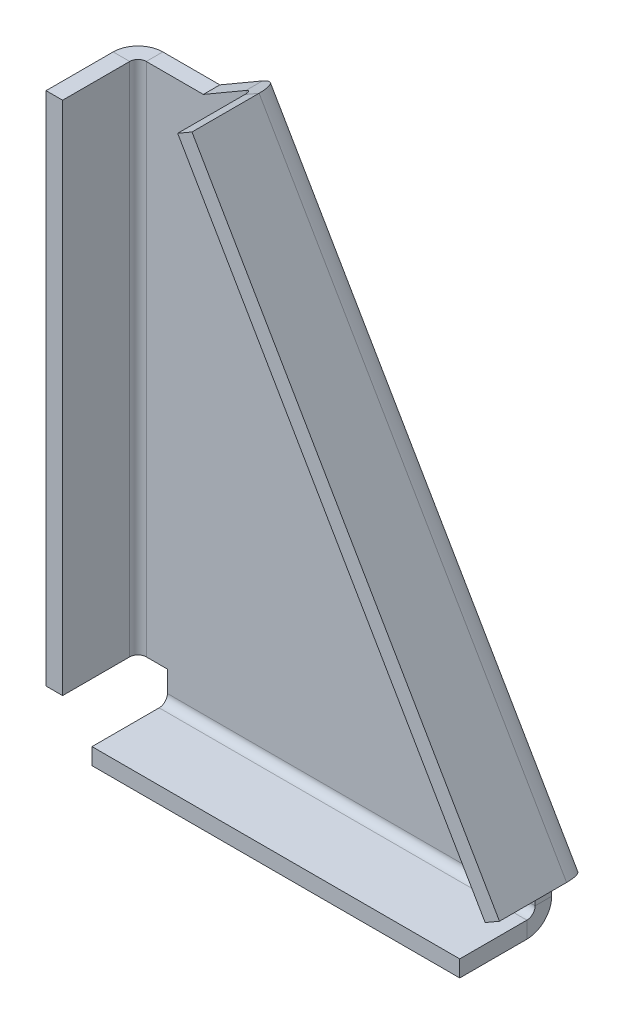
SolidWorks part; units mm, degrees
note: The reader was unsure of these and kept them because the rebuilt part matched: flange length of "Edge-Flange1".
material "6061 Alloy"
ref_plane "Front Plane" through (0, 0, 0) normal (0, 0, 1) x (1, 0, 0)
ref_plane "Top Plane" through (0, 0, 0) normal (0, 1, 0) x (1, 0, 0)
ref_plane "Right Plane" through (0, 0, 0) normal (1, 0, 0) x (0, 0, -1)
sketch "Sketch1" plane through (0, 0, 0) normal (0, 0, 1) x (1, 0, 0)
  line L0 (0, 0) -> (0, -6.35)
  line L1 (0, -6.35) -> (50.8, -6.35)
  line L2 (50.8, -6.35) -> (50.8, 0)
  line L3 (50.8, 0) -> (56.2919, 3.1877)
  line L4 (56.2919, 3.1877) -> (13.8112, 76.3748)
  line L5 (13.8112, 76.3748) -> (4.9644, 71.2397)
  line L6 (4.9644, 71.2397) -> (-6.35, 71.2397)
  line L7 (-6.35, 71.2397) -> (-6.35, 0)
  line L8 (-6.35, 0) -> (0, 0)
  point P10 (9.4496, 71.2397)
  point P11 (4.9644, 71.2397)
  dimension "D1" = 50.8
  dimension "D3" = 6.35
base flange "Base-Flange1" sketch "Sketch1" thickness 2.286 reverse thickness direction no parameters "D1"=1.143
edge flange "Edge-Flange1" sketch "Sketch12" flange profiles "Sketch12", "Sketch13", "Sketch14" flange angle 90 flange length 12.7 flange position material inside bend radius 1.143 thickness 2.286 relief rectangular gap distance 1 parameters "D6"=10, "D8"=1
sketch "Sketch12" plane through (-6.35, 0, 0) normal (-1, 0, 0) x (0, -1, 0)
  line L0 (-71.2397, 0) -> (0, 0) construction
  line L1 (-71.2397, 0) -> (0, 0)
  line L2 (-71.2397, 0) -> (-71.2397, 10.414)
  line L3 (-71.2397, 10.414) -> (0, 10.414)
  line L4 (0, 10.414) -> (0, 0)
sketch "Sketch13" plane through (0, -6.35, 0) normal (0, -1, 0) x (1, 0, 0)
  line L0 (0, 0) -> (50.8, 0) construction
  line L1 (0, 0) -> (50.8, 0)
  line L2 (0, 0) -> (0, 10.414)
  line L3 (0, 10.414) -> (50.8, 10.414)
  line L4 (50.8, 10.414) -> (50.8, 0)
sketch "Sketch14" plane through (43.4899, 25.2433, 0) normal (0.8649, 0.502, 0) x (-0.502, 0.8649, 0)
  line L0 (-25.5018, 0) -> (59.1207, 0) construction
  line L1 (-25.5018, 0) -> (59.1207, 0)
  line L2 (-25.5018, 0) -> (-25.5018, 10.414)
  line L3 (-25.5018, 10.414) -> (59.1207, 10.414)
  line L4 (59.1207, 10.414) -> (59.1207, 0)
bend "EdgeBend1" bend radius 1.143 bend angle 90 parameters "D5"=1
bend "EdgeBend2" bend radius 1.143 bend angle 90 parameters "D5"=2
bend "EdgeBend3" bend radius 1.143 bend angle 90 parameters "D5"=3
sketch "Bend-Lines1" [suppressed] plane through (0, 0, 0) normal (0, 1, 0) x (1, 0, 0)
sketch "Bounding-Box1" [suppressed] plane through (0, 0, 0) normal (0, 1, 0) x (1, 0, 0)
sheet metal parameters "Sheet-Metal1" thickness 2.286 parameters "D1"=1.143
flat pattern "Flat-Pattern1" [suppressed]
sketch "Bend-Lines2" plane through (0, 0, 0) normal (0, 1, 0) x (1, 0, 0)
sketch3d "Bounding-Box2" [suppressed]
  line L0 (-68.6901, 88.5048, 0) -> (-68.6901, -6.35, 0) construction
  line L1 (6.35, 88.5048, 0) -> (6.35, -6.35, 0) construction
  line L2 (-68.6901, 88.5048, 0) -> (6.35, 88.5048, 0) construction
  line L3 (-68.6901, -6.35, 0) -> (6.35, -6.35, 0) construction
sheet metal parameters "Sheet-Metal2" thickness 2.286 parameters "D1"=1.143
flat pattern "Flat-Pattern1"
sketch "Bend-Lines2" plane through (0, 0, 0) normal (0, 0, 1) x (1, 0, 0)
  line L0 (54.6772, 2.2505) -> (12.1965, 75.4375) construction
  line L1 (0, -4.483) -> (50.8, -4.483) construction
  line L2 (-4.483, 71.2397) -> (-4.483, 0) construction
  line L3 (54.6772, 2.2505) -> (12.1965, 75.4375) construction
  line L4 (0, -4.483) -> (50.8, -4.483) construction
  line L5 (-4.483, 71.2397) -> (-4.483, 0) construction
sketch3d "Bounding-Box2" [suppressed]
  line L0 (64.0463, 80.8757, 0) -> (64.0463, -15.316, 0) construction
  line L1 (-15.316, 80.8757, 0) -> (-15.316, -15.316, 0) construction
  line L2 (64.0463, 80.8757, 0) -> (-15.316, 80.8757, 0) construction
  line L3 (64.0463, -15.316, 0) -> (-15.316, -15.316, 0) construction
bend of the flat pattern "Flatten-<EdgeBend1>1"
bend of the flat pattern "Flatten-<EdgeBend2>1"
bend of the flat pattern "Flatten-<EdgeBend3>1"
